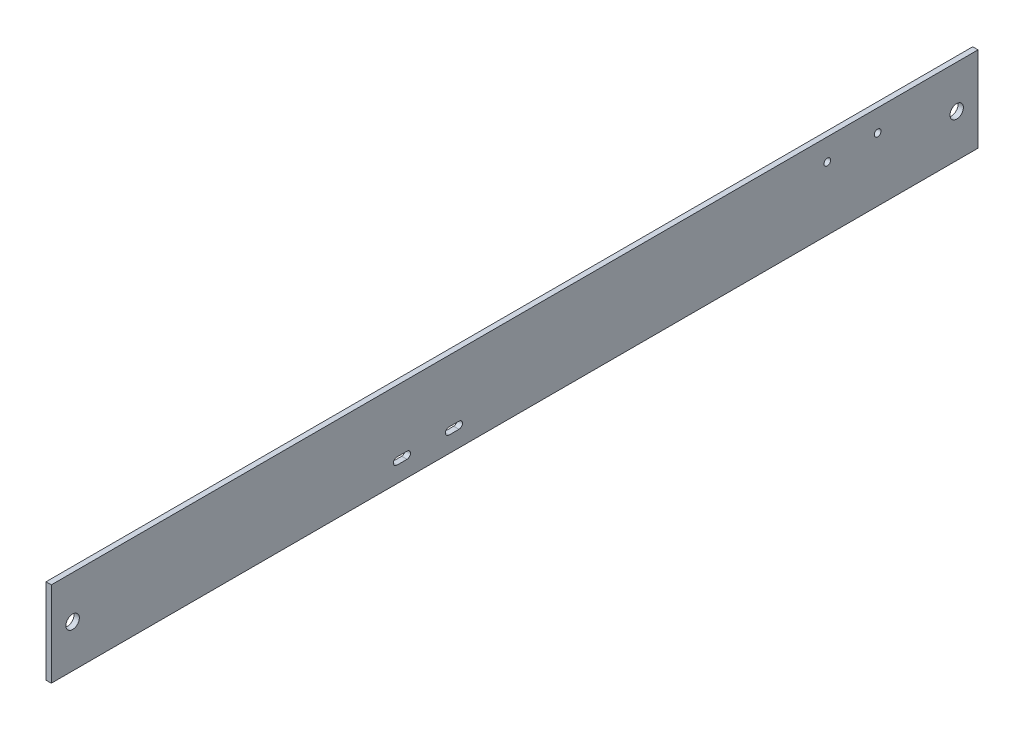
SolidWorks part; units mm, degrees
ref_plane "Front Plane" through (0, 0, 0) normal (0, 0, 1) x (1, 0, 0)
ref_plane "Top Plane" through (0, 0, 0) normal (0, 1, 0) x (1, 0, 0)
ref_plane "Right Plane" through (0, 0, 0) normal (1, 0, 0) x (0, 0, -1)
sketch "Sketch1" plane through (0, 0, 0) normal (1, 0, 0) x (0, 0, -1)
  line L0 (206.025, 11.7) -> (212.025, 11.7) construction
  line L1 (0, 0) -> (552.45, 0)
  line L2 (0, 0) -> (0, 50.8)
  line L3 (0, 50.8) -> (552.45, 50.8)
  line L4 (552.45, 0) -> (552.45, 50.8)
  line L5 (206.025, 13.8) -> (212.025, 13.8)
  line L6 (206.025, 9.6) -> (212.025, 9.6)
  line L7 (237.025, 11.7) -> (243.025, 11.7) construction
  line L8 (237.025, 13.8) -> (243.025, 13.8)
  line L9 (237.025, 9.6) -> (243.025, 9.6)
  circle A0 centre (12.7, 25.4) radius 4
  circle A1 centre (539.75, 25.4) radius 4
  arc A2 (206.025, 13.8) -> (206.025, 9.6) centre (206.025, 11.7) ccw
  arc A3 (212.025, 9.6) -> (212.025, 13.8) centre (212.025, 11.7) ccw
  arc A4 (237.025, 13.8) -> (237.025, 9.6) centre (237.025, 11.7) ccw
  arc A5 (243.025, 9.6) -> (243.025, 13.8) centre (243.025, 11.7) ccw
  circle A6 centre (462.625, 37.8) radius 2
  circle A7 centre (492.625, 37.8) radius 2
  point P11 (209.025, 11.7)
  point P16 (240.025, 11.7)
  dimension "D3" = 8
  dimension "D8" = 4.2
  dimension "D17" = 4
  dimension "D1" = 50.8
  dimension "D2" = 552.45
  dimension "D4" = 25.4
  dimension "D5" = 12.7
  dimension "D6" = 12.7
  dimension "D7" = 6
  dimension "D9" = 31
  dimension "D10" = 39.1
  dimension "D11" = 209.025
  dimension "D12" = 240.025
  dimension "D13" = 539.75
  dimension "D14" = 30
  dimension "D15" = 59.825
  dimension "D16" = 13
  dimension "D18" = 462.625
extrude "Boss-Extrude2" add sketch "Sketch1" along normal blind 3.175
equation "\"RailThickness\"= .125in'Spec"
equation "\"VSWidth\"= 1.25in'Spec"
equation "\"SideRailLength\"= 21.75in"
equation "\"LowerRailHeight\"= 2.0in"
equation "\"StepperHolePadSize\"= \"StepperHoleDiameter\""
equation "\"DistanceFromFrontSideToFirstLeftStepperHoleMountYSValue\"= 74.025mm"
equation "\"DistanceBetweenFrontToBackStepperHoles\"= \"BedLength\" - \"BuildPlateStandoffHolesDistanceFromFrontOrBackSide\" * 2'Equals 270"
equation "\"BedLength\"= \"BuildPlateLength\""
equation "\"D1@Sketch1\"=\"LowerRailHeight\""
equation "\"D2@Sketch1\"=\"SideRailLength\""
equation "\"FrameFastenerHoleDiameter\"= 8mm"
equation "\"D3@Sketch1\"=\"FrameFastenerHoleDiameter\""
equation "\"D4@Sketch1\"=\"LowerRailHeight\"/2"
equation "\"D5@Sketch1\"=\"FrameFastenerHoleOffsetFromEdge\""
equation "\"D6@Sketch1\"=\"FrameFastenerHoleOffsetFromEdge\""
equation "\"D8@Sketch1\"=\"StepperMountSlotDiameterOnRails\""
equation "\"D1@Boss-Extrude2\"=\"RailThickness\""
equation "\"FrameFastenerHoleOffsetFromEdge\"= \"VSWidth\" / 2 - \"GapBetweenVerticalSupportsAndRails\" / 2"
equation "\"StepperMountSlotDiameterOnRails\"= 4.2mm"
equation "\"StepperMountSlotWidth\"= 6mm"
equation "\"Nema17StepperMountSlotDistance\"= 31mm'Spec"
equation "\"D9@Sketch1\"=\"Nema17StepperMountSlotDistance\""
equation "\"D7@Sketch1\"=\"StepperMountSlotWidth\""
equation "\"BuildPlateLength\"= 352mm'Spec"
equation "\"BuildPlateStandoffHolesDistanceFromFrontOrBackSide\"= 41mm"
equation "\"D10@Sketch1\"=\"OffsetToGive10mmZAxisMovement\""
equation "\"DistanceFromFrontSideToMidRightStepperHoleMount\"= \"DistanceFromFrontSideToFirstLeftStepperHoleMountYSValue\" + \"DistanceBetweenFrontToBackStepperHoles\" / 2'Equals 209.025"
equation "\"D11@Sketch1\"=\"DistanceFromFrontSideToMidRightStepperHoleMount\""
equation "\"OffsetToGive10mmZAxisMovement\"= \"LowerRailHeight\" / 2 + 13.7mm'Allow Stepper 10mm Vertical movement"
equation "\"GapBetweenVerticalSupportsAndRails\"= \"RailThickness\" * 2"
equation "\"AngleBracketSmallHoleDiameter\"= 4mm"
equation "\"AngleBracketSlotDistanceBetweenHoles\"= 30mm"
equation "\"AngleBracketSlotDistanceFromTop\"= 13mm"
equation "\"AngleBracketSlotDistanceFromCorner\"= \"AngleBracketSlotDistanceFromBack\" - \"GapBetweenVerticalSupportsAndRails\" / 2'Equals 61.825"
equation "\"AngleBracketSlotDistanceFromBack\"= 65mm"
equation "\"D14@Sketch1\"=\"AngleBracketSlotDistanceBetweenHoles\""
equation "\"D15@Sketch1\"= \"AngleBracketSlotDistanceFromCorner\" - 2mm'Minus 2mm to get screw hole in middle of slot"
equation "\"D16@Sketch1\"=\"AngleBracketSlotDistanceFromTop\""
equation "\"D17@Sketch1\"=\"AngleBracketSmallHoleDiameter\""
